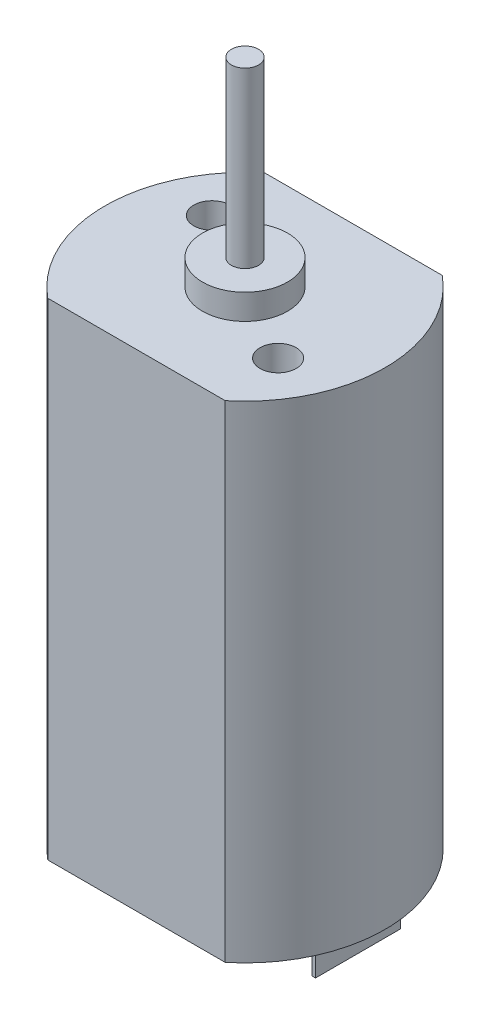
SolidWorks part; units mm, degrees
ref_plane "Front Plane" through (0, 0, 0) normal (0, 0, 1) x (1, 0, 0)
ref_plane "Top Plane" through (0, 0, 0) normal (0, 1, 0) x (1, 0, 0)
ref_plane "Right Plane" through (0, 0, 0) normal (1, 0, 0) x (0, 0, -1)
sketch "Sketch1" plane through (0, 0, 0) normal (0, 1, 0) x (1, 0, 0)
  line L0 (-4.9054, 6) -> (4.9054, 6)
  line L1 (4.9054, -6) -> (-4.9054, -6)
  arc A0 (-4.9054, 6) -> (-4.9054, -6) centre (0, 0) ccw
  arc A1 (4.9054, -6) -> (4.9054, 6) centre (0, 0) ccw
  dimension "D1" = 7.75
  dimension "D2" = 12
extrude "Boss-Extrude1" add sketch "Sketch1" along normal mid plane 26.9
sketch "Sketch2" plane through (0, 13.45, 0) normal (0, 1, 0) x (1, 0, 0)
  circle A0 centre (0, 0) radius 2.35
  dimension "D1" = 4.7
extrude "Boss-Extrude2" add sketch "Sketch2" along normal blind 1.4
sketch "Sketch3" plane through (0, 14.85, 0) normal (0, 1, 0) x (1, 0, 0)
  circle A0 centre (0, 0) radius 0.75
  dimension "D1" = 1.5
extrude "Boss-Extrude5" add sketch "Sketch3" along normal blind 9.6
sketch "Sketch4" plane through (0, -13.45, 0) normal (0, -1, 0) x (1, 0, 0)
  line L0 (-6.05, 0) -> (6.05, 0) construction
  line L1 (-6.25, 2.35) -> (-6.05, 2.35)
  line L2 (-6.25, 2.35) -> (-6.25, -2.35)
  line L3 (-6.25, -2.35) -> (-6.05, -2.35)
  line L4 (-6.05, 2.35) -> (-6.05, -2.35)
  line L5 (6.05, 2.35) -> (6.25, 2.35)
  line L6 (6.05, 2.35) -> (6.05, -2.35)
  line L7 (6.05, -2.35) -> (6.25, -2.35)
  line L8 (6.25, 2.35) -> (6.25, -2.35)
  dimension "D1" = 0.2
  dimension "D2" = 12.1
  dimension "D3" = 4.7
extrude "Boss-Extrude6" add sketch "Sketch4" along normal blind 1.9
sketch "Sketch5" plane through (0, 13.45, 0) normal (0, 1, 0) x (1, 0, 0)
  line L0 (-4.3301, 2.5) -> (4.3301, -2.5) construction
  line L1 (0, 0) -> (-5.6857, 0) construction
  circle A0 centre (-4.3301, 2.5) radius 1
  circle A1 centre (4.3301, -2.5) radius 1
  dimension "D3" = 2
  dimension "D1" = 30
  dimension "D2" = 10
extrude "Cut-Extrude1" cut sketch "Sketch5" against normal blind 1.9
ref_axis "Axis1" through (0, 15.9889, 0) along (0, -1, 0)
move or copy body "Body-Move/Copy1" [suppressed] bodies to move or copy 105
